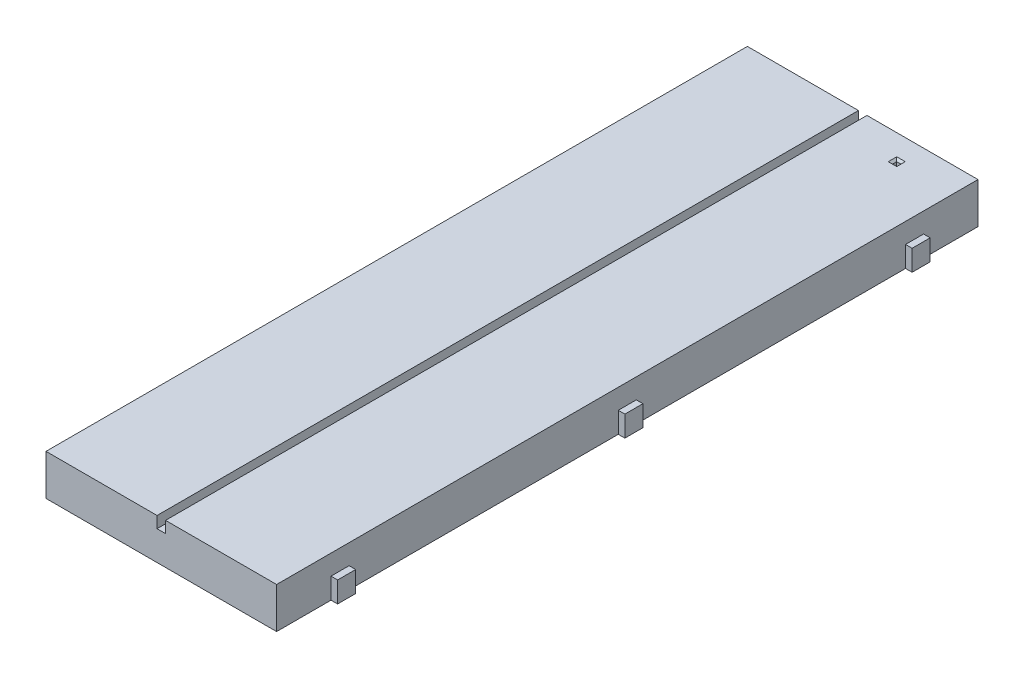
SolidWorks part; units mm, degrees
ref_plane "Front Plane" through (0, 0, 0) normal (0, 0, 1) x (1, 0, 0)
ref_plane "Top Plane" through (0, 0, 0) normal (0, 1, 0) x (1, 0, 0)
ref_plane "Right Plane" through (0, 0, 0) normal (1, 0, 0) x (0, 0, -1)
sketch "Sketch1" plane through (0, 0, 0) normal (0, 1, 0) x (1, 0, 0)
  line L1 (-27.125, -82.5) -> (27.125, -82.5)
  line L2 (-27.125, -82.5) -> (-27.125, 82.5)
  line L3 (-27.125, 82.5) -> (27.125, 82.5)
  line L4 (27.125, -82.5) -> (27.125, 82.5)
  line L5 (-27.125, -82.5) -> (27.125, 82.5) construction
  line L6 (-27.125, 82.5) -> (27.125, -82.5) construction
  point P0 (0, 0)
  dimension "D1" = 54.25
  dimension "D2" = 165
extrude "Boss-Extrude1" add sketch "Sketch1" against normal blind 9.6
sketch "Sketch2" plane through (27.125, 0, 0) normal (1, 0, 0) x (0, 0, -1)
  line L0 (82.5, -4.7) -> (69.7, -4.7)
  line L1 (82.5, -9.6) -> (82.5, 0) construction
  line L2 (-82.5, -9.6) -> (82.5, -9.6) construction
  line L3 (69.7, -4.7) -> (65.45, -4.7)
  line L4 (69.7, -4.7) -> (69.7, -9.6)
  line L5 (69.7, -9.6) -> (65.45, -9.6)
  line L6 (65.45, -4.7) -> (65.45, -9.6)
  line L7 (0, 0) -> (0, -9.6)
  line L8 (-2.125, -4.7) -> (2.125, -4.7)
  line L9 (-2.125, -4.7) -> (-2.125, -9.6)
  line L10 (-2.125, -9.6) -> (2.125, -9.6)
  line L11 (2.125, -4.7) -> (2.125, -9.6)
  line L12 (-2.125, -4.7) -> (2.125, -9.6) construction
  line L13 (-2.125, -9.6) -> (2.125, -4.7) construction
  line L14 (-69.7, -9.6) -> (-65.45, -9.6)
  line L15 (-65.45, -4.7) -> (-65.45, -9.6)
  line L16 (-69.7, -4.7) -> (-65.45, -4.7)
  line L17 (-69.7, -4.7) -> (-69.7, -9.6)
  line L18 (-69.7, -4.7) -> (-82.5, -4.8)
  line L19 (-82.5, -9.6) -> (-82.5, 0) construction
  point P9 (0, -7.15)
  line M14 (-82.5, -9.6) -> (82.5, -9.6)
  dimension "D1" = 12.8
  dimension "D2" = 4.9
  dimension "D3" = 4.25
  dimension "D4" = 4.25
  dimension "D5" = 4.9
  dimension "D6" = 12.8
extrude "Boss-Extrude2" add sketch "Sketch2" along normal blind 1.55 and the other way blind 1.55 contours L16 L17 L15 M14 | L3 L6 L4 M14 | L8 L11 L10 L9 region at (27.125, -7.15, -67.575) region at (27.125, -7.15, 67.575)
sketch "Sketch15" plane through (-27.125, 0, 0) normal (-1, 0, 0) x (0, 0, 1)
  line L0 (82.5, -9.6) -> (82.5, 0) construction
  line L2 (-82.5, -9.6) -> (82.5, -9.6) construction
  line L3 (69.7, -4.7) -> (65.45, -4.7)
  line L4 (69.7, -4.7) -> (69.7, -9.6)
  line L5 (69.7, -9.6) -> (65.45, -9.6)
  line L6 (65.45, -4.7) -> (65.45, -9.6)
  line L7 (-69.7, -9.6) -> (-65.45, -9.6)
  line L8 (-65.45, -4.7) -> (-65.45, -9.6)
  line L9 (-69.7, -4.7) -> (-65.45, -4.7)
  line L10 (-2.125, -4.7) -> (2.125, -4.7)
  line L11 (-2.125, -4.7) -> (-2.125, -9.6)
  line L12 (-2.125, -9.6) -> (2.125, -9.6)
  line L13 (2.125, -4.7) -> (2.125, -9.6)
  line L14 (-2.125, -4.7) -> (2.125, -9.6) construction
  line L15 (-2.125, -9.6) -> (2.125, -4.7) construction
  line L16 (-69.7, -4.7) -> (-69.7, -9.6)
  point P3 (0, -4.7)
  point P9 (67.575, -7.15)
  point P12 (0, -4.7)
  dimension "D1" = 4.25
  dimension "D2" = 4.9
  dimension "D3" = 12.8
  dimension "D4" = 4.25
  dimension "D5" = 4.9
extrude "Cut-Extrude1" cut sketch "Sketch15" against normal blind 1.55
sketch "Sketch17" plane through (0, 0, 0) normal (0, 1, 0) x (1, 0, 0)
  line L0 (27.125, 82.5) -> (-27.125, 82.5) construction
  line L1 (-1, -82.5) -> (1, -82.5)
  line L2 (-1, -82.5) -> (-1, 82.5)
  line L3 (-1, 82.5) -> (1, 82.5)
  line L4 (1, -82.5) -> (1, 82.5)
  line L5 (-1, -82.5) -> (1, 82.5) construction
  line L6 (-1, 82.5) -> (1, -82.5) construction
  point P0 (0, 0)
  dimension "D1" = 2
extrude "Cut-Extrude2" cut sketch "Sketch17" against normal blind 2.7
sketch "Sketch18" plane through (0, 0, 0) normal (0, 1, 0) x (1, 0, 0)
  line L0 (27.125, 82.5) -> (14.425, 82.5)
  line L1 (27.125, 82.5) -> (1, 82.5) construction
  line L2 (14.425, 82.5) -> (14.425, 77.0807)
  line L3 (11.925, 77.0807) -> (11.925, 76.0807)
  line L4 (14.425, 77.0807) -> (13.425, 77.0807)
  line L5 (14.425, 77.0807) -> (14.425, 76.0807)
  line L6 (14.425, 76.0807) -> (13.425, 76.0807)
  line L7 (13.425, 77.0807) -> (13.425, 76.0807)
  line L8 (11.925, 77.0807) -> (10.925, 77.0807)
  line L9 (10.925, 77.0807) -> (10.925, 76.0807)
  line L10 (11.925, 76.0807) -> (10.925, 76.0807)
  line L11 (9.425, 77.0807) -> (9.425, 76.0807)
  line L12 (9.425, 77.0807) -> (8.425, 77.0807)
  line L13 (8.425, 77.0807) -> (8.425, 76.0807)
  line L14 (9.425, 76.0807) -> (8.425, 76.0807)
  line L15 (6.925, 77.0807) -> (6.925, 76.0807)
  line L16 (6.925, 77.0807) -> (5.925, 77.0807)
  line L17 (5.925, 77.0807) -> (5.925, 76.0807)
  line L18 (6.925, 76.0807) -> (5.925, 76.0807)
  line L19 (4.425, 77.0807) -> (4.425, 76.0807)
  line L20 (4.425, 77.0807) -> (3.425, 77.0807)
  line L21 (3.425, 77.0807) -> (3.425, 76.0807)
  line L22 (4.425, 76.0807) -> (3.425, 76.0807)
  line L23 (11.925, 74.5807) -> (11.925, 73.5807)
  line L24 (11.925, 74.5807) -> (10.925, 74.5807)
  line L25 (10.925, 74.5807) -> (10.925, 73.5807)
  line L26 (11.925, 73.5807) -> (10.925, 73.5807)
  line L27 (9.425, 74.5807) -> (9.425, 73.5807)
  line L28 (9.425, 74.5807) -> (8.425, 74.5807)
  line L29 (8.425, 74.5807) -> (8.425, 73.5807)
  line L30 (9.425, 73.5807) -> (8.425, 73.5807)
  line L31 (6.925, 74.5807) -> (6.925, 73.5807)
  line L32 (6.925, 74.5807) -> (5.925, 74.5807)
  line L33 (5.925, 74.5807) -> (5.925, 73.5807)
  line L34 (6.925, 73.5807) -> (5.925, 73.5807)
  line L35 (4.425, 74.5807) -> (4.425, 73.5807)
  line L36 (4.425, 74.5807) -> (3.425, 74.5807)
  line L37 (3.425, 74.5807) -> (3.425, 73.5807)
  line L38 (4.425, 73.5807) -> (3.425, 73.5807)
  line L39 (11.925, 72.0807) -> (11.925, 71.0807)
  line L40 (11.925, 72.0807) -> (10.925, 72.0807)
  line L41 (10.925, 72.0807) -> (10.925, 71.0807)
  line L42 (11.925, 71.0807) -> (10.925, 71.0807)
  line L43 (9.425, 72.0807) -> (9.425, 71.0807)
  line L44 (9.425, 72.0807) -> (8.425, 72.0807)
  line L45 (8.425, 72.0807) -> (8.425, 71.0807)
  line L46 (9.425, 71.0807) -> (8.425, 71.0807)
  line L47 (6.925, 72.0807) -> (6.925, 71.0807)
  line L48 (6.925, 72.0807) -> (5.925, 72.0807)
  line L49 (5.925, 72.0807) -> (5.925, 71.0807)
  line L50 (6.925, 71.0807) -> (5.925, 71.0807)
  line L51 (4.425, 72.0807) -> (4.425, 71.0807)
  line L52 (4.425, 72.0807) -> (3.425, 72.0807)
  line L53 (3.425, 72.0807) -> (3.425, 71.0807)
  line L54 (4.425, 71.0807) -> (3.425, 71.0807)
  line L55 (11.925, 69.5807) -> (11.925, 68.5807)
  line L56 (11.925, 69.5807) -> (10.925, 69.5807)
  line L57 (10.925, 69.5807) -> (10.925, 68.5807)
  line L58 (11.925, 68.5807) -> (10.925, 68.5807)
  line L59 (9.425, 69.5807) -> (9.425, 68.5807)
  line L60 (9.425, 69.5807) -> (8.425, 69.5807)
  line L61 (8.425, 69.5807) -> (8.425, 68.5807)
  line L62 (9.425, 68.5807) -> (8.425, 68.5807)
  line L63 (6.925, 69.5807) -> (6.925, 68.5807)
  line L64 (6.925, 69.5807) -> (5.925, 69.5807)
  line L65 (5.925, 69.5807) -> (5.925, 68.5807)
  line L66 (6.925, 68.5807) -> (5.925, 68.5807)
  line L67 (4.425, 69.5807) -> (4.425, 68.5807)
  line L68 (4.425, 69.5807) -> (3.425, 69.5807)
  line L69 (3.425, 69.5807) -> (3.425, 68.5807)
  line L70 (4.425, 68.5807) -> (3.425, 68.5807)
  line L71 (11.925, 67.0807) -> (11.925, 66.0807)
  line L72 (11.925, 67.0807) -> (10.925, 67.0807)
  line L73 (10.925, 67.0807) -> (10.925, 66.0807)
  line L74 (11.925, 66.0807) -> (10.925, 66.0807)
  line L75 (9.425, 67.0807) -> (9.425, 66.0807)
  line L76 (9.425, 67.0807) -> (8.425, 67.0807)
  line L77 (8.425, 67.0807) -> (8.425, 66.0807)
  line L78 (9.425, 66.0807) -> (8.425, 66.0807)
  line L79 (6.925, 67.0807) -> (6.925, 66.0807)
  line L80 (6.925, 67.0807) -> (5.925, 67.0807)
  line L81 (5.925, 67.0807) -> (5.925, 66.0807)
  line L82 (6.925, 66.0807) -> (5.925, 66.0807)
  line L83 (4.425, 67.0807) -> (4.425, 66.0807)
  line L84 (4.425, 67.0807) -> (3.425, 67.0807)
  line L85 (3.425, 67.0807) -> (3.425, 66.0807)
  line L86 (4.425, 66.0807) -> (3.425, 66.0807)
  line L87 (11.925, 64.5807) -> (11.925, 63.5807)
  line L88 (11.925, 64.5807) -> (10.925, 64.5807)
  line L89 (10.925, 64.5807) -> (10.925, 63.5807)
  line L90 (11.925, 63.5807) -> (10.925, 63.5807)
  line L91 (9.425, 64.5807) -> (9.425, 63.5807)
  line L92 (9.425, 64.5807) -> (8.425, 64.5807)
  line L93 (8.425, 64.5807) -> (8.425, 63.5807)
  line L94 (9.425, 63.5807) -> (8.425, 63.5807)
  line L95 (6.925, 64.5807) -> (6.925, 63.5807)
  line L96 (6.925, 64.5807) -> (5.925, 64.5807)
  line L97 (5.925, 64.5807) -> (5.925, 63.5807)
  line L98 (6.925, 63.5807) -> (5.925, 63.5807)
  line L99 (4.425, 64.5807) -> (4.425, 63.5807)
  line L100 (4.425, 64.5807) -> (3.425, 64.5807)
  line L101 (3.425, 64.5807) -> (3.425, 63.5807)
  line L102 (4.425, 63.5807) -> (3.425, 63.5807)
  line L103 (11.925, 62.0807) -> (11.925, 61.0807)
  line L104 (11.925, 62.0807) -> (10.925, 62.0807)
  line L105 (10.925, 62.0807) -> (10.925, 61.0807)
  line L106 (11.925, 61.0807) -> (10.925, 61.0807)
  line L107 (9.425, 62.0807) -> (9.425, 61.0807)
  line L108 (9.425, 62.0807) -> (8.425, 62.0807)
  line L109 (8.425, 62.0807) -> (8.425, 61.0807)
  line L110 (9.425, 61.0807) -> (8.425, 61.0807)
  line L111 (6.925, 62.0807) -> (6.925, 61.0807)
  line L112 (6.925, 62.0807) -> (5.925, 62.0807)
  line L113 (5.925, 62.0807) -> (5.925, 61.0807)
  line L114 (6.925, 61.0807) -> (5.925, 61.0807)
  line L115 (4.425, 62.0807) -> (4.425, 61.0807)
  line L116 (4.425, 62.0807) -> (3.425, 62.0807)
  line L117 (3.425, 62.0807) -> (3.425, 61.0807)
  line L118 (4.425, 61.0807) -> (3.425, 61.0807)
  line L119 (11.925, 59.5807) -> (11.925, 58.5807)
  line L120 (11.925, 59.5807) -> (10.925, 59.5807)
  line L121 (10.925, 59.5807) -> (10.925, 58.5807)
  line L122 (11.925, 58.5807) -> (10.925, 58.5807)
  line L123 (9.425, 59.5807) -> (9.425, 58.5807)
  line L124 (9.425, 59.5807) -> (8.425, 59.5807)
  line L125 (8.425, 59.5807) -> (8.425, 58.5807)
  line L126 (9.425, 58.5807) -> (8.425, 58.5807)
  line L127 (6.925, 59.5807) -> (6.925, 58.5807)
  line L128 (6.925, 59.5807) -> (5.925, 59.5807)
  line L129 (5.925, 59.5807) -> (5.925, 58.5807)
  line L130 (6.925, 58.5807) -> (5.925, 58.5807)
  line L131 (4.425, 59.5807) -> (4.425, 58.5807)
  line L132 (4.425, 59.5807) -> (3.425, 59.5807)
  line L133 (3.425, 59.5807) -> (3.425, 58.5807)
  line L134 (4.425, 58.5807) -> (3.425, 58.5807)
  line L135 (11.925, 57.0807) -> (11.925, 56.0807)
  line L136 (11.925, 57.0807) -> (10.925, 57.0807)
  line L137 (10.925, 57.0807) -> (10.925, 56.0807)
  line L138 (11.925, 56.0807) -> (10.925, 56.0807)
  line L139 (9.425, 57.0807) -> (9.425, 56.0807)
  line L140 (9.425, 57.0807) -> (8.425, 57.0807)
  line L141 (8.425, 57.0807) -> (8.425, 56.0807)
  line L142 (9.425, 56.0807) -> (8.425, 56.0807)
  line L143 (6.925, 57.0807) -> (6.925, 56.0807)
  line L144 (6.925, 57.0807) -> (5.925, 57.0807)
  line L145 (5.925, 57.0807) -> (5.925, 56.0807)
  line L146 (6.925, 56.0807) -> (5.925, 56.0807)
  line L147 (4.425, 57.0807) -> (4.425, 56.0807)
  line L148 (4.425, 57.0807) -> (3.425, 57.0807)
  line L149 (3.425, 57.0807) -> (3.425, 56.0807)
  line L150 (4.425, 56.0807) -> (3.425, 56.0807)
  line L151 (11.925, 54.5807) -> (11.925, 53.5807)
  line L152 (11.925, 54.5807) -> (10.925, 54.5807)
  line L153 (10.925, 54.5807) -> (10.925, 53.5807)
  line L154 (11.925, 53.5807) -> (10.925, 53.5807)
  line L155 (9.425, 54.5807) -> (9.425, 53.5807)
  line L156 (9.425, 54.5807) -> (8.425, 54.5807)
  line L157 (8.425, 54.5807) -> (8.425, 53.5807)
  line L158 (9.425, 53.5807) -> (8.425, 53.5807)
  line L159 (6.925, 54.5807) -> (6.925, 53.5807)
  line L160 (6.925, 54.5807) -> (5.925, 54.5807)
  line L161 (5.925, 54.5807) -> (5.925, 53.5807)
  line L162 (6.925, 53.5807) -> (5.925, 53.5807)
  line L163 (4.425, 54.5807) -> (4.425, 53.5807)
  line L164 (4.425, 54.5807) -> (3.425, 54.5807)
  line L165 (3.425, 54.5807) -> (3.425, 53.5807)
  line L166 (4.425, 53.5807) -> (3.425, 53.5807)
  line L167 (11.925, 52.0807) -> (11.925, 51.0807)
  line L168 (11.925, 52.0807) -> (10.925, 52.0807)
  line L169 (10.925, 52.0807) -> (10.925, 51.0807)
  line L170 (11.925, 51.0807) -> (10.925, 51.0807)
  line L171 (9.425, 52.0807) -> (9.425, 51.0807)
  line L172 (9.425, 52.0807) -> (8.425, 52.0807)
  line L173 (8.425, 52.0807) -> (8.425, 51.0807)
  line L174 (9.425, 51.0807) -> (8.425, 51.0807)
  line L175 (6.925, 52.0807) -> (6.925, 51.0807)
  line L176 (6.925, 52.0807) -> (5.925, 52.0807)
  line L177 (5.925, 52.0807) -> (5.925, 51.0807)
  line L178 (6.925, 51.0807) -> (5.925, 51.0807)
  line L179 (4.425, 52.0807) -> (4.425, 51.0807)
  line L180 (4.425, 52.0807) -> (3.425, 52.0807)
  line L181 (3.425, 52.0807) -> (3.425, 51.0807)
  line L182 (4.425, 51.0807) -> (3.425, 51.0807)
  line L183 (11.925, 49.5807) -> (11.925, 48.5807)
  line L184 (11.925, 49.5807) -> (10.925, 49.5807)
  line L185 (10.925, 49.5807) -> (10.925, 48.5807)
  line L186 (11.925, 48.5807) -> (10.925, 48.5807)
  line L187 (9.425, 49.5807) -> (9.425, 48.5807)
  line L188 (9.425, 49.5807) -> (8.425, 49.5807)
  line L189 (8.425, 49.5807) -> (8.425, 48.5807)
  line L190 (9.425, 48.5807) -> (8.425, 48.5807)
  line L191 (6.925, 49.5807) -> (6.925, 48.5807)
  line L192 (6.925, 49.5807) -> (5.925, 49.5807)
  line L193 (5.925, 49.5807) -> (5.925, 48.5807)
  line L194 (6.925, 48.5807) -> (5.925, 48.5807)
  line L195 (4.425, 49.5807) -> (4.425, 48.5807)
  line L196 (4.425, 49.5807) -> (3.425, 49.5807)
  line L197 (3.425, 49.5807) -> (3.425, 48.5807)
  line L198 (4.425, 48.5807) -> (3.425, 48.5807)
  line L199 (11.925, 47.0807) -> (11.925, 46.0807)
  line L200 (11.925, 47.0807) -> (10.925, 47.0807)
  line L201 (10.925, 47.0807) -> (10.925, 46.0807)
  line L202 (11.925, 46.0807) -> (10.925, 46.0807)
  line L203 (9.425, 47.0807) -> (9.425, 46.0807)
  line L204 (9.425, 47.0807) -> (8.425, 47.0807)
  line L205 (8.425, 47.0807) -> (8.425, 46.0807)
  line L206 (9.425, 46.0807) -> (8.425, 46.0807)
  line L207 (6.925, 47.0807) -> (6.925, 46.0807)
  line L208 (6.925, 47.0807) -> (5.925, 47.0807)
  line L209 (5.925, 47.0807) -> (5.925, 46.0807)
  line L210 (6.925, 46.0807) -> (5.925, 46.0807)
  line L211 (4.425, 47.0807) -> (4.425, 46.0807)
  line L212 (4.425, 47.0807) -> (3.425, 47.0807)
  line L213 (3.425, 47.0807) -> (3.425, 46.0807)
  line L214 (4.425, 46.0807) -> (3.425, 46.0807)
  line L215 (11.925, 44.5807) -> (11.925, 43.5807)
  line L216 (11.925, 44.5807) -> (10.925, 44.5807)
  line L217 (10.925, 44.5807) -> (10.925, 43.5807)
  line L218 (11.925, 43.5807) -> (10.925, 43.5807)
  line L219 (9.425, 44.5807) -> (9.425, 43.5807)
  line L220 (9.425, 44.5807) -> (8.425, 44.5807)
  line L221 (8.425, 44.5807) -> (8.425, 43.5807)
  line L222 (9.425, 43.5807) -> (8.425, 43.5807)
  line L223 (6.925, 44.5807) -> (6.925, 43.5807)
  line L224 (6.925, 44.5807) -> (5.925, 44.5807)
  line L225 (5.925, 44.5807) -> (5.925, 43.5807)
  line L226 (6.925, 43.5807) -> (5.925, 43.5807)
  line L227 (4.425, 44.5807) -> (4.425, 43.5807)
  line L228 (4.425, 44.5807) -> (3.425, 44.5807)
  line L229 (3.425, 44.5807) -> (3.425, 43.5807)
  line L230 (4.425, 43.5807) -> (3.425, 43.5807)
  line L231 (11.925, 42.0807) -> (11.925, 41.0807)
  line L232 (11.925, 42.0807) -> (10.925, 42.0807)
  line L233 (10.925, 42.0807) -> (10.925, 41.0807)
  line L234 (11.925, 41.0807) -> (10.925, 41.0807)
  line L235 (9.425, 42.0807) -> (9.425, 41.0807)
  line L236 (9.425, 42.0807) -> (8.425, 42.0807)
  line L237 (8.425, 42.0807) -> (8.425, 41.0807)
  line L238 (9.425, 41.0807) -> (8.425, 41.0807)
  line L239 (6.925, 42.0807) -> (6.925, 41.0807)
  line L240 (6.925, 42.0807) -> (5.925, 42.0807)
  line L241 (5.925, 42.0807) -> (5.925, 41.0807)
  line L242 (6.925, 41.0807) -> (5.925, 41.0807)
  line L243 (4.425, 42.0807) -> (4.425, 41.0807)
  line L244 (4.425, 42.0807) -> (3.425, 42.0807)
  line L245 (3.425, 42.0807) -> (3.425, 41.0807)
  line L246 (4.425, 41.0807) -> (3.425, 41.0807)
  line L247 (11.925, 39.5807) -> (11.925, 38.5807)
  line L248 (11.925, 39.5807) -> (10.925, 39.5807)
  line L249 (10.925, 39.5807) -> (10.925, 38.5807)
  line L250 (11.925, 38.5807) -> (10.925, 38.5807)
  line L251 (9.425, 39.5807) -> (9.425, 38.5807)
  line L252 (9.425, 39.5807) -> (8.425, 39.5807)
  line L253 (8.425, 39.5807) -> (8.425, 38.5807)
  line L254 (9.425, 38.5807) -> (8.425, 38.5807)
  line L255 (6.925, 39.5807) -> (6.925, 38.5807)
  line L256 (6.925, 39.5807) -> (5.925, 39.5807)
  line L257 (5.925, 39.5807) -> (5.925, 38.5807)
  line L258 (6.925, 38.5807) -> (5.925, 38.5807)
  line L259 (4.425, 39.5807) -> (4.425, 38.5807)
  line L260 (4.425, 39.5807) -> (3.425, 39.5807)
  line L261 (3.425, 39.5807) -> (3.425, 38.5807)
  line L262 (4.425, 38.5807) -> (3.425, 38.5807)
  line L263 (11.925, 37.0807) -> (11.925, 36.0807)
  line L264 (11.925, 37.0807) -> (10.925, 37.0807)
  line L265 (10.925, 37.0807) -> (10.925, 36.0807)
  line L266 (11.925, 36.0807) -> (10.925, 36.0807)
  line L267 (9.425, 37.0807) -> (9.425, 36.0807)
  line L268 (9.425, 37.0807) -> (8.425, 37.0807)
  line L269 (8.425, 37.0807) -> (8.425, 36.0807)
  line L270 (9.425, 36.0807) -> (8.425, 36.0807)
  line L271 (6.925, 37.0807) -> (6.925, 36.0807)
  line L272 (6.925, 37.0807) -> (5.925, 37.0807)
  line L273 (5.925, 37.0807) -> (5.925, 36.0807)
  line L274 (6.925, 36.0807) -> (5.925, 36.0807)
  line L275 (4.425, 37.0807) -> (4.425, 36.0807)
  line L276 (4.425, 37.0807) -> (3.425, 37.0807)
  line L277 (3.425, 37.0807) -> (3.425, 36.0807)
  line L278 (4.425, 36.0807) -> (3.425, 36.0807)
  line L279 (11.925, 34.5807) -> (11.925, 33.5807)
  line L280 (11.925, 34.5807) -> (10.925, 34.5807)
  line L281 (10.925, 34.5807) -> (10.925, 33.5807)
  line L282 (11.925, 33.5807) -> (10.925, 33.5807)
  line L283 (9.425, 34.5807) -> (9.425, 33.5807)
  line L284 (9.425, 34.5807) -> (8.425, 34.5807)
  line L285 (8.425, 34.5807) -> (8.425, 33.5807)
  line L286 (9.425, 33.5807) -> (8.425, 33.5807)
  line L287 (6.925, 34.5807) -> (6.925, 33.5807)
  line L288 (6.925, 34.5807) -> (5.925, 34.5807)
  line L289 (5.925, 34.5807) -> (5.925, 33.5807)
  line L290 (6.925, 33.5807) -> (5.925, 33.5807)
  line L291 (4.425, 34.5807) -> (4.425, 33.5807)
  line L292 (4.425, 34.5807) -> (3.425, 34.5807)
  line L293 (3.425, 34.5807) -> (3.425, 33.5807)
  line L294 (4.425, 33.5807) -> (3.425, 33.5807)
  line L295 (11.925, 32.0807) -> (11.925, 31.0807)
  line L296 (11.925, 32.0807) -> (10.925, 32.0807)
  line L297 (10.925, 32.0807) -> (10.925, 31.0807)
  line L298 (11.925, 31.0807) -> (10.925, 31.0807)
  line L299 (9.425, 32.0807) -> (9.425, 31.0807)
  line L300 (9.425, 32.0807) -> (8.425, 32.0807)
  line L301 (8.425, 32.0807) -> (8.425, 31.0807)
  line L302 (9.425, 31.0807) -> (8.425, 31.0807)
  line L303 (6.925, 32.0807) -> (6.925, 31.0807)
  line L304 (6.925, 32.0807) -> (5.925, 32.0807)
  line L305 (5.925, 32.0807) -> (5.925, 31.0807)
  line L306 (6.925, 31.0807) -> (5.925, 31.0807)
  line L307 (4.425, 32.0807) -> (4.425, 31.0807)
  line L308 (4.425, 32.0807) -> (3.425, 32.0807)
  line L309 (3.425, 32.0807) -> (3.425, 31.0807)
  line L310 (4.425, 31.0807) -> (3.425, 31.0807)
  line L311 (11.925, 29.5807) -> (11.925, 28.5807)
  line L312 (11.925, 29.5807) -> (10.925, 29.5807)
  line L313 (10.925, 29.5807) -> (10.925, 28.5807)
  line L314 (11.925, 28.5807) -> (10.925, 28.5807)
  line L315 (9.425, 29.5807) -> (9.425, 28.5807)
  line L316 (9.425, 29.5807) -> (8.425, 29.5807)
  line L317 (8.425, 29.5807) -> (8.425, 28.5807)
  line L318 (9.425, 28.5807) -> (8.425, 28.5807)
  line L319 (6.925, 29.5807) -> (6.925, 28.5807)
  line L320 (6.925, 29.5807) -> (5.925, 29.5807)
  line L321 (5.925, 29.5807) -> (5.925, 28.5807)
  line L322 (6.925, 28.5807) -> (5.925, 28.5807)
  line L323 (4.425, 29.5807) -> (4.425, 28.5807)
  line L324 (4.425, 29.5807) -> (3.425, 29.5807)
  line L325 (3.425, 29.5807) -> (3.425, 28.5807)
  line L326 (4.425, 28.5807) -> (3.425, 28.5807)
  line L327 (11.925, 27.0807) -> (11.925, 26.0807)
  line L328 (11.925, 27.0807) -> (10.925, 27.0807)
  line L329 (10.925, 27.0807) -> (10.925, 26.0807)
  line L330 (11.925, 26.0807) -> (10.925, 26.0807)
  line L331 (9.425, 27.0807) -> (9.425, 26.0807)
  line L332 (9.425, 27.0807) -> (8.425, 27.0807)
  line L333 (8.425, 27.0807) -> (8.425, 26.0807)
  line L334 (9.425, 26.0807) -> (8.425, 26.0807)
  line L335 (6.925, 27.0807) -> (6.925, 26.0807)
  line L336 (6.925, 27.0807) -> (5.925, 27.0807)
  line L337 (5.925, 27.0807) -> (5.925, 26.0807)
  line L338 (6.925, 26.0807) -> (5.925, 26.0807)
  line L339 (4.425, 27.0807) -> (4.425, 26.0807)
  line L340 (4.425, 27.0807) -> (3.425, 27.0807)
  line L341 (3.425, 27.0807) -> (3.425, 26.0807)
  line L342 (4.425, 26.0807) -> (3.425, 26.0807)
  line L343 (11.925, 24.5807) -> (11.925, 23.5807)
  line L344 (11.925, 24.5807) -> (10.925, 24.5807)
  line L345 (10.925, 24.5807) -> (10.925, 23.5807)
  line L346 (11.925, 23.5807) -> (10.925, 23.5807)
  line L347 (9.425, 24.5807) -> (9.425, 23.5807)
  line L348 (9.425, 24.5807) -> (8.425, 24.5807)
  line L349 (8.425, 24.5807) -> (8.425, 23.5807)
  line L350 (9.425, 23.5807) -> (8.425, 23.5807)
  line L351 (6.925, 24.5807) -> (6.925, 23.5807)
  line L352 (6.925, 24.5807) -> (5.925, 24.5807)
  line L353 (5.925, 24.5807) -> (5.925, 23.5807)
  line L354 (6.925, 23.5807) -> (5.925, 23.5807)
  line L355 (4.425, 24.5807) -> (4.425, 23.5807)
  line L356 (4.425, 24.5807) -> (3.425, 24.5807)
  line L357 (3.425, 24.5807) -> (3.425, 23.5807)
  line L358 (4.425, 23.5807) -> (3.425, 23.5807)
  line L359 (11.925, 22.0807) -> (11.925, 21.0807)
  line L360 (11.925, 22.0807) -> (10.925, 22.0807)
  line L361 (10.925, 22.0807) -> (10.925, 21.0807)
  line L362 (11.925, 21.0807) -> (10.925, 21.0807)
  line L363 (9.425, 22.0807) -> (9.425, 21.0807)
  line L364 (9.425, 22.0807) -> (8.425, 22.0807)
  line L365 (8.425, 22.0807) -> (8.425, 21.0807)
  line L366 (9.425, 21.0807) -> (8.425, 21.0807)
  line L367 (6.925, 22.0807) -> (6.925, 21.0807)
  line L368 (6.925, 22.0807) -> (5.925, 22.0807)
  line L369 (5.925, 22.0807) -> (5.925, 21.0807)
  line L370 (6.925, 21.0807) -> (5.925, 21.0807)
  line L371 (4.425, 22.0807) -> (4.425, 21.0807)
  line L372 (4.425, 22.0807) -> (3.425, 22.0807)
  line L373 (3.425, 22.0807) -> (3.425, 21.0807)
  line L374 (4.425, 21.0807) -> (3.425, 21.0807)
  line L375 (11.925, 19.5807) -> (11.925, 18.5807)
  line L376 (11.925, 19.5807) -> (10.925, 19.5807)
  line L377 (10.925, 19.5807) -> (10.925, 18.5807)
  line L378 (11.925, 18.5807) -> (10.925, 18.5807)
  line L379 (9.425, 19.5807) -> (9.425, 18.5807)
  line L380 (9.425, 19.5807) -> (8.425, 19.5807)
  line L381 (8.425, 19.5807) -> (8.425, 18.5807)
  line L382 (9.425, 18.5807) -> (8.425, 18.5807)
  line L383 (6.925, 19.5807) -> (6.925, 18.5807)
  line L384 (6.925, 19.5807) -> (5.925, 19.5807)
  line L385 (5.925, 19.5807) -> (5.925, 18.5807)
  line L386 (6.925, 18.5807) -> (5.925, 18.5807)
  line L387 (4.425, 19.5807) -> (4.425, 18.5807)
  line L388 (4.425, 19.5807) -> (3.425, 19.5807)
  line L389 (3.425, 19.5807) -> (3.425, 18.5807)
  line L390 (4.425, 18.5807) -> (3.425, 18.5807)
  line L391 (11.925, 17.0807) -> (11.925, 16.0807)
  line L392 (11.925, 17.0807) -> (10.925, 17.0807)
  line L393 (10.925, 17.0807) -> (10.925, 16.0807)
  line L394 (11.925, 16.0807) -> (10.925, 16.0807)
  line L395 (9.425, 17.0807) -> (9.425, 16.0807)
  line L396 (9.425, 17.0807) -> (8.425, 17.0807)
  line L397 (8.425, 17.0807) -> (8.425, 16.0807)
  line L398 (9.425, 16.0807) -> (8.425, 16.0807)
  line L399 (6.925, 17.0807) -> (6.925, 16.0807)
  line L400 (6.925, 17.0807) -> (5.925, 17.0807)
  line L401 (5.925, 17.0807) -> (5.925, 16.0807)
  line L402 (6.925, 16.0807) -> (5.925, 16.0807)
  line L403 (4.425, 17.0807) -> (4.425, 16.0807)
  line L404 (4.425, 17.0807) -> (3.425, 17.0807)
  line L405 (3.425, 17.0807) -> (3.425, 16.0807)
  line L406 (4.425, 16.0807) -> (3.425, 16.0807)
  line L407 (11.925, 14.5807) -> (11.925, 13.5807)
  line L408 (11.925, 14.5807) -> (10.925, 14.5807)
  line L409 (10.925, 14.5807) -> (10.925, 13.5807)
  line L410 (11.925, 13.5807) -> (10.925, 13.5807)
  line L411 (9.425, 14.5807) -> (9.425, 13.5807)
  line L412 (9.425, 14.5807) -> (8.425, 14.5807)
  line L413 (8.425, 14.5807) -> (8.425, 13.5807)
  line L414 (9.425, 13.5807) -> (8.425, 13.5807)
  line L415 (6.925, 14.5807) -> (6.925, 13.5807)
  line L416 (6.925, 14.5807) -> (5.925, 14.5807)
  line L417 (5.925, 14.5807) -> (5.925, 13.5807)
  line L418 (6.925, 13.5807) -> (5.925, 13.5807)
  line L419 (4.425, 14.5807) -> (4.425, 13.5807)
  line L420 (4.425, 14.5807) -> (3.425, 14.5807)
  line L421 (3.425, 14.5807) -> (3.425, 13.5807)
  line L422 (4.425, 13.5807) -> (3.425, 13.5807)
  line L423 (11.925, 12.0807) -> (11.925, 11.0807)
  line L424 (11.925, 12.0807) -> (10.925, 12.0807)
  line L425 (10.925, 12.0807) -> (10.925, 11.0807)
  line L426 (11.925, 11.0807) -> (10.925, 11.0807)
  line L427 (9.425, 12.0807) -> (9.425, 11.0807)
  line L428 (9.425, 12.0807) -> (8.425, 12.0807)
  line L429 (8.425, 12.0807) -> (8.425, 11.0807)
  line L430 (9.425, 11.0807) -> (8.425, 11.0807)
  line L431 (6.925, 12.0807) -> (6.925, 11.0807)
  line L432 (6.925, 12.0807) -> (5.925, 12.0807)
  line L433 (5.925, 12.0807) -> (5.925, 11.0807)
  line L434 (6.925, 11.0807) -> (5.925, 11.0807)
  line L435 (4.425, 12.0807) -> (4.425, 11.0807)
  line L436 (4.425, 12.0807) -> (3.425, 12.0807)
  line L437 (3.425, 12.0807) -> (3.425, 11.0807)
  line L438 (4.425, 11.0807) -> (3.425, 11.0807)
  line L439 (11.925, 9.5807) -> (11.925, 8.5807)
  line L440 (11.925, 9.5807) -> (10.925, 9.5807)
  line L441 (10.925, 9.5807) -> (10.925, 8.5807)
  line L442 (11.925, 8.5807) -> (10.925, 8.5807)
  line L443 (9.425, 9.5807) -> (9.425, 8.5807)
  line L444 (9.425, 9.5807) -> (8.425, 9.5807)
  line L445 (8.425, 9.5807) -> (8.425, 8.5807)
  line L446 (9.425, 8.5807) -> (8.425, 8.5807)
  line L447 (6.925, 9.5807) -> (6.925, 8.5807)
  line L448 (6.925, 9.5807) -> (5.925, 9.5807)
  line L449 (5.925, 9.5807) -> (5.925, 8.5807)
  line L450 (6.925, 8.5807) -> (5.925, 8.5807)
  line L451 (4.425, 9.5807) -> (4.425, 8.5807)
  line L452 (4.425, 9.5807) -> (3.425, 9.5807)
  line L453 (3.425, 9.5807) -> (3.425, 8.5807)
  line L454 (4.425, 8.5807) -> (3.425, 8.5807)
  line L455 (11.925, 7.0807) -> (11.925, 6.0807)
  line L456 (11.925, 7.0807) -> (10.925, 7.0807)
  line L457 (10.925, 7.0807) -> (10.925, 6.0807)
  line L458 (11.925, 6.0807) -> (10.925, 6.0807)
  line L459 (9.425, 7.0807) -> (9.425, 6.0807)
  line L460 (9.425, 7.0807) -> (8.425, 7.0807)
  line L461 (8.425, 7.0807) -> (8.425, 6.0807)
  line L462 (9.425, 6.0807) -> (8.425, 6.0807)
  line L463 (6.925, 7.0807) -> (6.925, 6.0807)
  line L464 (6.925, 7.0807) -> (5.925, 7.0807)
  line L465 (5.925, 7.0807) -> (5.925, 6.0807)
  line L466 (6.925, 6.0807) -> (5.925, 6.0807)
  line L467 (4.425, 7.0807) -> (4.425, 6.0807)
  line L468 (4.425, 7.0807) -> (3.425, 7.0807)
  line L469 (3.425, 7.0807) -> (3.425, 6.0807)
  line L470 (4.425, 6.0807) -> (3.425, 6.0807)
  line L471 (11.925, 4.5807) -> (11.925, 3.5807)
  line L472 (11.925, 4.5807) -> (10.925, 4.5807)
  line L473 (10.925, 4.5807) -> (10.925, 3.5807)
  line L474 (11.925, 3.5807) -> (10.925, 3.5807)
  line L475 (9.425, 4.5807) -> (9.425, 3.5807)
  line L476 (9.425, 4.5807) -> (8.425, 4.5807)
  line L477 (8.425, 4.5807) -> (8.425, 3.5807)
  line L478 (9.425, 3.5807) -> (8.425, 3.5807)
  line L479 (6.925, 4.5807) -> (6.925, 3.5807)
  line L480 (6.925, 4.5807) -> (5.925, 4.5807)
  line L481 (5.925, 4.5807) -> (5.925, 3.5807)
  line L482 (6.925, 3.5807) -> (5.925, 3.5807)
  line L483 (4.425, 4.5807) -> (4.425, 3.5807)
  line L484 (4.425, 4.5807) -> (3.425, 4.5807)
  line L485 (3.425, 4.5807) -> (3.425, 3.5807)
  line L486 (4.425, 3.5807) -> (3.425, 3.5807)
  line L487 (11.925, 2.0807) -> (11.925, 1.0807)
  line L488 (11.925, 2.0807) -> (10.925, 2.0807)
  line L489 (10.925, 2.0807) -> (10.925, 1.0807)
  line L490 (11.925, 1.0807) -> (10.925, 1.0807)
  line L491 (9.425, 2.0807) -> (9.425, 1.0807)
  line L492 (9.425, 2.0807) -> (8.425, 2.0807)
  line L493 (8.425, 2.0807) -> (8.425, 1.0807)
  line L494 (9.425, 1.0807) -> (8.425, 1.0807)
  line L495 (6.925, 2.0807) -> (6.925, 1.0807)
  line L496 (6.925, 2.0807) -> (5.925, 2.0807)
  line L497 (5.925, 2.0807) -> (5.925, 1.0807)
  line L498 (6.925, 1.0807) -> (5.925, 1.0807)
  line L499 (4.425, 2.0807) -> (4.425, 1.0807)
  line L500 (4.425, 2.0807) -> (3.425, 2.0807)
  line L501 (3.425, 2.0807) -> (3.425, 1.0807)
  line L502 (4.425, 1.0807) -> (3.425, 1.0807)
  line L503 (11.925, -0.4193) -> (11.925, -1.4193)
  line L504 (11.925, -0.4193) -> (10.925, -0.4193)
  line L505 (10.925, -0.4193) -> (10.925, -1.4193)
  line L506 (11.925, -1.4193) -> (10.925, -1.4193)
  line L507 (9.425, -0.4193) -> (9.425, -1.4193)
  line L508 (9.425, -0.4193) -> (8.425, -0.4193)
  line L509 (8.425, -0.4193) -> (8.425, -1.4193)
  line L510 (9.425, -1.4193) -> (8.425, -1.4193)
  line L511 (6.925, -0.4193) -> (6.925, -1.4193)
  line L512 (6.925, -0.4193) -> (5.925, -0.4193)
  line L513 (5.925, -0.4193) -> (5.925, -1.4193)
  line L514 (6.925, -1.4193) -> (5.925, -1.4193)
  line L515 (4.425, -0.4193) -> (4.425, -1.4193)
  line L516 (4.425, -0.4193) -> (3.425, -0.4193)
  line L517 (3.425, -0.4193) -> (3.425, -1.4193)
  line L518 (4.425, -1.4193) -> (3.425, -1.4193)
  line L519 (11.925, -2.9193) -> (11.925, -3.9193)
  line L520 (11.925, -2.9193) -> (10.925, -2.9193)
  line L521 (10.925, -2.9193) -> (10.925, -3.9193)
  line L522 (11.925, -3.9193) -> (10.925, -3.9193)
  line L523 (9.425, -2.9193) -> (9.425, -3.9193)
  line L524 (9.425, -2.9193) -> (8.425, -2.9193)
  line L525 (8.425, -2.9193) -> (8.425, -3.9193)
  line L526 (9.425, -3.9193) -> (8.425, -3.9193)
  line L527 (6.925, -2.9193) -> (6.925, -3.9193)
  line L528 (6.925, -2.9193) -> (5.925, -2.9193)
  line L529 (5.925, -2.9193) -> (5.925, -3.9193)
  line L530 (6.925, -3.9193) -> (5.925, -3.9193)
  line L531 (4.425, -2.9193) -> (4.425, -3.9193)
  line L532 (4.425, -2.9193) -> (3.425, -2.9193)
  line L533 (3.425, -2.9193) -> (3.425, -3.9193)
  line L534 (4.425, -3.9193) -> (3.425, -3.9193)
  line L535 (11.925, -5.4193) -> (11.925, -6.4193)
  line L536 (11.925, -5.4193) -> (10.925, -5.4193)
  line L537 (10.925, -5.4193) -> (10.925, -6.4193)
  line L538 (11.925, -6.4193) -> (10.925, -6.4193)
  line L539 (9.425, -5.4193) -> (9.425, -6.4193)
  line L540 (9.425, -5.4193) -> (8.425, -5.4193)
  line L541 (8.425, -5.4193) -> (8.425, -6.4193)
  line L542 (9.425, -6.4193) -> (8.425, -6.4193)
  line L543 (6.925, -5.4193) -> (6.925, -6.4193)
  line L544 (6.925, -5.4193) -> (5.925, -5.4193)
  line L545 (5.925, -5.4193) -> (5.925, -6.4193)
  line L546 (6.925, -6.4193) -> (5.925, -6.4193)
  line L547 (4.425, -5.4193) -> (4.425, -6.4193)
  line L548 (4.425, -5.4193) -> (3.425, -5.4193)
  line L549 (3.425, -5.4193) -> (3.425, -6.4193)
  line L550 (4.425, -6.4193) -> (3.425, -6.4193)
  line L551 (11.925, -7.9193) -> (11.925, -8.9193)
  line L552 (11.925, -7.9193) -> (10.925, -7.9193)
  line L553 (10.925, -7.9193) -> (10.925, -8.9193)
  line L554 (11.925, -8.9193) -> (10.925, -8.9193)
  line L555 (9.425, -7.9193) -> (9.425, -8.9193)
  line L556 (9.425, -7.9193) -> (8.425, -7.9193)
  line L557 (8.425, -7.9193) -> (8.425, -8.9193)
  line L558 (9.425, -8.9193) -> (8.425, -8.9193)
  line L559 (6.925, -7.9193) -> (6.925, -8.9193)
  line L560 (6.925, -7.9193) -> (5.925, -7.9193)
  line L561 (5.925, -7.9193) -> (5.925, -8.9193)
  line L562 (6.925, -8.9193) -> (5.925, -8.9193)
  line L563 (4.425, -7.9193) -> (4.425, -8.9193)
  line L564 (4.425, -7.9193) -> (3.425, -7.9193)
  line L565 (3.425, -7.9193) -> (3.425, -8.9193)
  line L566 (4.425, -8.9193) -> (3.425, -8.9193)
  line L567 (11.925, -10.4193) -> (11.925, -11.4193)
  line L568 (11.925, -10.4193) -> (10.925, -10.4193)
  line L569 (10.925, -10.4193) -> (10.925, -11.4193)
  line L570 (11.925, -11.4193) -> (10.925, -11.4193)
  line L571 (9.425, -10.4193) -> (9.425, -11.4193)
  line L572 (9.425, -10.4193) -> (8.425, -10.4193)
  line L573 (8.425, -10.4193) -> (8.425, -11.4193)
  line L574 (9.425, -11.4193) -> (8.425, -11.4193)
  line L575 (6.925, -10.4193) -> (6.925, -11.4193)
  line L576 (6.925, -10.4193) -> (5.925, -10.4193)
  line L577 (5.925, -10.4193) -> (5.925, -11.4193)
  line L578 (6.925, -11.4193) -> (5.925, -11.4193)
  line L579 (4.425, -10.4193) -> (4.425, -11.4193)
  line L580 (4.425, -10.4193) -> (3.425, -10.4193)
  line L581 (3.425, -10.4193) -> (3.425, -11.4193)
  line L582 (4.425, -11.4193) -> (3.425, -11.4193)
  line L583 (11.925, -12.9193) -> (11.925, -13.9193)
  line L584 (11.925, -12.9193) -> (10.925, -12.9193)
  line L585 (10.925, -12.9193) -> (10.925, -13.9193)
  line L586 (11.925, -13.9193) -> (10.925, -13.9193)
  line L587 (9.425, -12.9193) -> (9.425, -13.9193)
  line L588 (9.425, -12.9193) -> (8.425, -12.9193)
  line L589 (8.425, -12.9193) -> (8.425, -13.9193)
  line L590 (9.425, -13.9193) -> (8.425, -13.9193)
  line L591 (6.925, -12.9193) -> (6.925, -13.9193)
  line L592 (6.925, -12.9193) -> (5.925, -12.9193)
  line L593 (5.925, -12.9193) -> (5.925, -13.9193)
  line L594 (6.925, -13.9193) -> (5.925, -13.9193)
  line L595 (4.425, -12.9193) -> (4.425, -13.9193)
  line L596 (4.425, -12.9193) -> (3.425, -12.9193)
  line L597 (3.425, -12.9193) -> (3.425, -13.9193)
  line L598 (4.425, -13.9193) -> (3.425, -13.9193)
  line L599 (11.925, -15.4193) -> (11.925, -16.4193)
  line L600 (11.925, -15.4193) -> (10.925, -15.4193)
  line L601 (10.925, -15.4193) -> (10.925, -16.4193)
  line L602 (11.925, -16.4193) -> (10.925, -16.4193)
  line L603 (9.425, -15.4193) -> (9.425, -16.4193)
  line L604 (9.425, -15.4193) -> (8.425, -15.4193)
  line L605 (8.425, -15.4193) -> (8.425, -16.4193)
  line L606 (9.425, -16.4193) -> (8.425, -16.4193)
  line L607 (6.925, -15.4193) -> (6.925, -16.4193)
  line L608 (6.925, -15.4193) -> (5.925, -15.4193)
  line L609 (5.925, -15.4193) -> (5.925, -16.4193)
  line L610 (6.925, -16.4193) -> (5.925, -16.4193)
  line L611 (4.425, -15.4193) -> (4.425, -16.4193)
  line L612 (4.425, -15.4193) -> (3.425, -15.4193)
  line L613 (3.425, -15.4193) -> (3.425, -16.4193)
  line L614 (4.425, -16.4193) -> (3.425, -16.4193)
  line L615 (11.925, -17.9193) -> (11.925, -18.9193)
  line L616 (11.925, -17.9193) -> (10.925, -17.9193)
  line L617 (10.925, -17.9193) -> (10.925, -18.9193)
  line L618 (11.925, -18.9193) -> (10.925, -18.9193)
  line L619 (9.425, -17.9193) -> (9.425, -18.9193)
  line L620 (9.425, -17.9193) -> (8.425, -17.9193)
  line L621 (8.425, -17.9193) -> (8.425, -18.9193)
  line L622 (9.425, -18.9193) -> (8.425, -18.9193)
  line L623 (6.925, -17.9193) -> (6.925, -18.9193)
  line L624 (6.925, -17.9193) -> (5.925, -17.9193)
  line L625 (5.925, -17.9193) -> (5.925, -18.9193)
  line L626 (6.925, -18.9193) -> (5.925, -18.9193)
  line L627 (4.425, -17.9193) -> (4.425, -18.9193)
  line L628 (4.425, -17.9193) -> (3.425, -17.9193)
  line L629 (3.425, -17.9193) -> (3.425, -18.9193)
  line L630 (4.425, -18.9193) -> (3.425, -18.9193)
  line L631 (11.925, -20.4193) -> (11.925, -21.4193)
  line L632 (11.925, -20.4193) -> (10.925, -20.4193)
  line L633 (10.925, -20.4193) -> (10.925, -21.4193)
  line L634 (11.925, -21.4193) -> (10.925, -21.4193)
  line L635 (9.425, -20.4193) -> (9.425, -21.4193)
  line L636 (9.425, -20.4193) -> (8.425, -20.4193)
  line L637 (8.425, -20.4193) -> (8.425, -21.4193)
  line L638 (9.425, -21.4193) -> (8.425, -21.4193)
  line L639 (6.925, -20.4193) -> (6.925, -21.4193)
  line L640 (6.925, -20.4193) -> (5.925, -20.4193)
  line L641 (5.925, -20.4193) -> (5.925, -21.4193)
  line L642 (6.925, -21.4193) -> (5.925, -21.4193)
  line L643 (4.425, -20.4193) -> (4.425, -21.4193)
  line L644 (4.425, -20.4193) -> (3.425, -20.4193)
  line L645 (3.425, -20.4193) -> (3.425, -21.4193)
  line L646 (4.425, -21.4193) -> (3.425, -21.4193)
  line L647 (11.925, -22.9193) -> (11.925, -23.9193)
  line L648 (11.925, -22.9193) -> (10.925, -22.9193)
  line L649 (10.925, -22.9193) -> (10.925, -23.9193)
  line L650 (11.925, -23.9193) -> (10.925, -23.9193)
  line L651 (9.425, -22.9193) -> (9.425, -23.9193)
  line L652 (9.425, -22.9193) -> (8.425, -22.9193)
  line L653 (8.425, -22.9193) -> (8.425, -23.9193)
  line L654 (9.425, -23.9193) -> (8.425, -23.9193)
  line L655 (6.925, -22.9193) -> (6.925, -23.9193)
  line L656 (6.925, -22.9193) -> (5.925, -22.9193)
  line L657 (5.925, -22.9193) -> (5.925, -23.9193)
  line L658 (6.925, -23.9193) -> (5.925, -23.9193)
  line L659 (4.425, -22.9193) -> (4.425, -23.9193)
  line L660 (4.425, -22.9193) -> (3.425, -22.9193)
  line L661 (3.425, -22.9193) -> (3.425, -23.9193)
  line L662 (4.425, -23.9193) -> (3.425, -23.9193)
  line L663 (11.925, -25.4193) -> (11.925, -26.4193)
  line L664 (11.925, -25.4193) -> (10.925, -25.4193)
  line L665 (10.925, -25.4193) -> (10.925, -26.4193)
  line L666 (11.925, -26.4193) -> (10.925, -26.4193)
  line L667 (9.425, -25.4193) -> (9.425, -26.4193)
  line L668 (9.425, -25.4193) -> (8.425, -25.4193)
  line L669 (8.425, -25.4193) -> (8.425, -26.4193)
  line L670 (9.425, -26.4193) -> (8.425, -26.4193)
  line L671 (6.925, -25.4193) -> (6.925, -26.4193)
  line L672 (6.925, -25.4193) -> (5.925, -25.4193)
  line L673 (5.925, -25.4193) -> (5.925, -26.4193)
  line L674 (6.925, -26.4193) -> (5.925, -26.4193)
  line L675 (4.425, -25.4193) -> (4.425, -26.4193)
  line L676 (4.425, -25.4193) -> (3.425, -25.4193)
  line L677 (3.425, -25.4193) -> (3.425, -26.4193)
  line L678 (4.425, -26.4193) -> (3.425, -26.4193)
  line L679 (11.925, -27.9193) -> (11.925, -28.9193)
  line L680 (11.925, -27.9193) -> (10.925, -27.9193)
  line L681 (10.925, -27.9193) -> (10.925, -28.9193)
  line L682 (11.925, -28.9193) -> (10.925, -28.9193)
  line L683 (9.425, -27.9193) -> (9.425, -28.9193)
  line L684 (9.425, -27.9193) -> (8.425, -27.9193)
  line L685 (8.425, -27.9193) -> (8.425, -28.9193)
  line L686 (9.425, -28.9193) -> (8.425, -28.9193)
  line L687 (6.925, -27.9193) -> (6.925, -28.9193)
  line L688 (6.925, -27.9193) -> (5.925, -27.9193)
  line L689 (5.925, -27.9193) -> (5.925, -28.9193)
  line L690 (6.925, -28.9193) -> (5.925, -28.9193)
  line L691 (4.425, -27.9193) -> (4.425, -28.9193)
  line L692 (4.425, -27.9193) -> (3.425, -27.9193)
  line L693 (3.425, -27.9193) -> (3.425, -28.9193)
  line L694 (4.425, -28.9193) -> (3.425, -28.9193)
  line L695 (11.925, -30.4193) -> (11.925, -31.4193)
  line L696 (11.925, -30.4193) -> (10.925, -30.4193)
  line L697 (10.925, -30.4193) -> (10.925, -31.4193)
  line L698 (11.925, -31.4193) -> (10.925, -31.4193)
  line L699 (9.425, -30.4193) -> (9.425, -31.4193)
  line L700 (9.425, -30.4193) -> (8.425, -30.4193)
  line L701 (8.425, -30.4193) -> (8.425, -31.4193)
  line L702 (9.425, -31.4193) -> (8.425, -31.4193)
  line L703 (6.925, -30.4193) -> (6.925, -31.4193)
  line L704 (6.925, -30.4193) -> (5.925, -30.4193)
  line L705 (5.925, -30.4193) -> (5.925, -31.4193)
  line L706 (6.925, -31.4193) -> (5.925, -31.4193)
  line L707 (4.425, -30.4193) -> (4.425, -31.4193)
  line L708 (4.425, -30.4193) -> (3.425, -30.4193)
  line L709 (3.425, -30.4193) -> (3.425, -31.4193)
  line L710 (4.425, -31.4193) -> (3.425, -31.4193)
  line L711 (11.925, -32.9193) -> (11.925, -33.9193)
  line L712 (11.925, -32.9193) -> (10.925, -32.9193)
  line L713 (10.925, -32.9193) -> (10.925, -33.9193)
  line L714 (11.925, -33.9193) -> (10.925, -33.9193)
  line L715 (9.425, -32.9193) -> (9.425, -33.9193)
  line L716 (9.425, -32.9193) -> (8.425, -32.9193)
  line L717 (8.425, -32.9193) -> (8.425, -33.9193)
  line L718 (9.425, -33.9193) -> (8.425, -33.9193)
  line L719 (6.925, -32.9193) -> (6.925, -33.9193)
  line L720 (6.925, -32.9193) -> (5.925, -32.9193)
  line L721 (5.925, -32.9193) -> (5.925, -33.9193)
  line L722 (6.925, -33.9193) -> (5.925, -33.9193)
  line L723 (4.425, -32.9193) -> (4.425, -33.9193)
  line L724 (4.425, -32.9193) -> (3.425, -32.9193)
  line L725 (3.425, -32.9193) -> (3.425, -33.9193)
  line L726 (4.425, -33.9193) -> (3.425, -33.9193)
  line L727 (11.925, -35.4193) -> (11.925, -36.4193)
  line L728 (11.925, -35.4193) -> (10.925, -35.4193)
  line L729 (10.925, -35.4193) -> (10.925, -36.4193)
  line L730 (11.925, -36.4193) -> (10.925, -36.4193)
  line L731 (9.425, -35.4193) -> (9.425, -36.4193)
  line L732 (9.425, -35.4193) -> (8.425, -35.4193)
  line L733 (8.425, -35.4193) -> (8.425, -36.4193)
  line L734 (9.425, -36.4193) -> (8.425, -36.4193)
  line L735 (6.925, -35.4193) -> (6.925, -36.4193)
  line L736 (6.925, -35.4193) -> (5.925, -35.4193)
  line L737 (5.925, -35.4193) -> (5.925, -36.4193)
  line L738 (6.925, -36.4193) -> (5.925, -36.4193)
  line L739 (4.425, -35.4193) -> (4.425, -36.4193)
  line L740 (4.425, -35.4193) -> (3.425, -35.4193)
  line L741 (3.425, -35.4193) -> (3.425, -36.4193)
  line L742 (4.425, -36.4193) -> (3.425, -36.4193)
  line L743 (11.925, -37.9193) -> (11.925, -38.9193)
  line L744 (11.925, -37.9193) -> (10.925, -37.9193)
  line L745 (10.925, -37.9193) -> (10.925, -38.9193)
  line L746 (11.925, -38.9193) -> (10.925, -38.9193)
  line L747 (9.425, -37.9193) -> (9.425, -38.9193)
  line L748 (9.425, -37.9193) -> (8.425, -37.9193)
  line L749 (8.425, -37.9193) -> (8.425, -38.9193)
  line L750 (9.425, -38.9193) -> (8.425, -38.9193)
  line L751 (6.925, -37.9193) -> (6.925, -38.9193)
  line L752 (6.925, -37.9193) -> (5.925, -37.9193)
  line L753 (5.925, -37.9193) -> (5.925, -38.9193)
  line L754 (6.925, -38.9193) -> (5.925, -38.9193)
  line L755 (4.425, -37.9193) -> (4.425, -38.9193)
  line L756 (4.425, -37.9193) -> (3.425, -37.9193)
  line L757 (3.425, -37.9193) -> (3.425, -38.9193)
  line L758 (4.425, -38.9193) -> (3.425, -38.9193)
  line L759 (11.925, -40.4193) -> (11.925, -41.4193)
  line L760 (11.925, -40.4193) -> (10.925, -40.4193)
  line L761 (10.925, -40.4193) -> (10.925, -41.4193)
  line L762 (11.925, -41.4193) -> (10.925, -41.4193)
  line L763 (9.425, -40.4193) -> (9.425, -41.4193)
  line L764 (9.425, -40.4193) -> (8.425, -40.4193)
  line L765 (8.425, -40.4193) -> (8.425, -41.4193)
  line L766 (9.425, -41.4193) -> (8.425, -41.4193)
  line L767 (6.925, -40.4193) -> (6.925, -41.4193)
  line L768 (6.925, -40.4193) -> (5.925, -40.4193)
  line L769 (5.925, -40.4193) -> (5.925, -41.4193)
  line L770 (6.925, -41.4193) -> (5.925, -41.4193)
  line L771 (4.425, -40.4193) -> (4.425, -41.4193)
  line L772 (4.425, -40.4193) -> (3.425, -40.4193)
  line L773 (3.425, -40.4193) -> (3.425, -41.4193)
  line L774 (4.425, -41.4193) -> (3.425, -41.4193)
  line L775 (11.925, -42.9193) -> (11.925, -43.9193)
  line L776 (11.925, -42.9193) -> (10.925, -42.9193)
  line L777 (10.925, -42.9193) -> (10.925, -43.9193)
  line L778 (11.925, -43.9193) -> (10.925, -43.9193)
  line L779 (9.425, -42.9193) -> (9.425, -43.9193)
  line L780 (9.425, -42.9193) -> (8.425, -42.9193)
  line L781 (8.425, -42.9193) -> (8.425, -43.9193)
  line L782 (9.425, -43.9193) -> (8.425, -43.9193)
  line L783 (6.925, -42.9193) -> (6.925, -43.9193)
  line L784 (6.925, -42.9193) -> (5.925, -42.9193)
  line L785 (5.925, -42.9193) -> (5.925, -43.9193)
  line L786 (6.925, -43.9193) -> (5.925, -43.9193)
  line L787 (4.425, -42.9193) -> (4.425, -43.9193)
  line L788 (4.425, -42.9193) -> (3.425, -42.9193)
  line L789 (3.425, -42.9193) -> (3.425, -43.9193)
  line L790 (4.425, -43.9193) -> (3.425, -43.9193)
  line L791 (11.925, -45.4193) -> (11.925, -46.4193)
  line L792 (11.925, -45.4193) -> (10.925, -45.4193)
  line L793 (10.925, -45.4193) -> (10.925, -46.4193)
  line L794 (11.925, -46.4193) -> (10.925, -46.4193)
  line L795 (9.425, -45.4193) -> (9.425, -46.4193)
  line L796 (9.425, -45.4193) -> (8.425, -45.4193)
  line L797 (8.425, -45.4193) -> (8.425, -46.4193)
  line L798 (9.425, -46.4193) -> (8.425, -46.4193)
  line L799 (6.925, -45.4193) -> (6.925, -46.4193)
  line L800 (6.925, -45.4193) -> (5.925, -45.4193)
  line L801 (5.925, -45.4193) -> (5.925, -46.4193)
  line L802 (6.925, -46.4193) -> (5.925, -46.4193)
  line L803 (4.425, -45.4193) -> (4.425, -46.4193)
  line L804 (4.425, -45.4193) -> (3.425, -45.4193)
  line L805 (3.425, -45.4193) -> (3.425, -46.4193)
  line L806 (4.425, -46.4193) -> (3.425, -46.4193)
  line L807 (11.925, -47.9193) -> (11.925, -48.9193)
  line L808 (11.925, -47.9193) -> (10.925, -47.9193)
  line L809 (10.925, -47.9193) -> (10.925, -48.9193)
  line L810 (11.925, -48.9193) -> (10.925, -48.9193)
  line L811 (9.425, -47.9193) -> (9.425, -48.9193)
  line L812 (9.425, -47.9193) -> (8.425, -47.9193)
  line L813 (8.425, -47.9193) -> (8.425, -48.9193)
  line L814 (9.425, -48.9193) -> (8.425, -48.9193)
  line L815 (6.925, -47.9193) -> (6.925, -48.9193)
  line L816 (6.925, -47.9193) -> (5.925, -47.9193)
  line L817 (5.925, -47.9193) -> (5.925, -48.9193)
  line L818 (6.925, -48.9193) -> (5.925, -48.9193)
  line L819 (4.425, -47.9193) -> (4.425, -48.9193)
  line L820 (4.425, -47.9193) -> (3.425, -47.9193)
  line L821 (3.425, -47.9193) -> (3.425, -48.9193)
  line L822 (4.425, -48.9193) -> (3.425, -48.9193)
  line L823 (11.925, -50.4193) -> (11.925, -51.4193)
  line L824 (11.925, -50.4193) -> (10.925, -50.4193)
  line L825 (10.925, -50.4193) -> (10.925, -51.4193)
  line L826 (11.925, -51.4193) -> (10.925, -51.4193)
  line L827 (9.425, -50.4193) -> (9.425, -51.4193)
  line L828 (9.425, -50.4193) -> (8.425, -50.4193)
  line L829 (8.425, -50.4193) -> (8.425, -51.4193)
  line L830 (9.425, -51.4193) -> (8.425, -51.4193)
  line L831 (6.925, -50.4193) -> (6.925, -51.4193)
  line L832 (6.925, -50.4193) -> (5.925, -50.4193)
  line L833 (5.925, -50.4193) -> (5.925, -51.4193)
  line L834 (6.925, -51.4193) -> (5.925, -51.4193)
  line L835 (4.425, -50.4193) -> (4.425, -51.4193)
  line L836 (4.425, -50.4193) -> (3.425, -50.4193)
  line L837 (3.425, -50.4193) -> (3.425, -51.4193)
  line L838 (4.425, -51.4193) -> (3.425, -51.4193)
  line L839 (11.925, -52.9193) -> (11.925, -53.9193)
  line L840 (11.925, -52.9193) -> (10.925, -52.9193)
  line L841 (10.925, -52.9193) -> (10.925, -53.9193)
  line L842 (11.925, -53.9193) -> (10.925, -53.9193)
  line L843 (9.425, -52.9193) -> (9.425, -53.9193)
  line L844 (9.425, -52.9193) -> (8.425, -52.9193)
  line L845 (8.425, -52.9193) -> (8.425, -53.9193)
  line L846 (9.425, -53.9193) -> (8.425, -53.9193)
  line L847 (6.925, -52.9193) -> (6.925, -53.9193)
  line L848 (6.925, -52.9193) -> (5.925, -52.9193)
  line L849 (5.925, -52.9193) -> (5.925, -53.9193)
  line L850 (6.925, -53.9193) -> (5.925, -53.9193)
  line L851 (4.425, -52.9193) -> (4.425, -53.9193)
  line L852 (4.425, -52.9193) -> (3.425, -52.9193)
  line L853 (3.425, -52.9193) -> (3.425, -53.9193)
  line L854 (4.425, -53.9193) -> (3.425, -53.9193)
  line L855 (11.925, -55.4193) -> (11.925, -56.4193)
  line L856 (11.925, -55.4193) -> (10.925, -55.4193)
  line L857 (10.925, -55.4193) -> (10.925, -56.4193)
  line L858 (11.925, -56.4193) -> (10.925, -56.4193)
  line L859 (9.425, -55.4193) -> (9.425, -56.4193)
  line L860 (9.425, -55.4193) -> (8.425, -55.4193)
  line L861 (8.425, -55.4193) -> (8.425, -56.4193)
  line L862 (9.425, -56.4193) -> (8.425, -56.4193)
  line L863 (6.925, -55.4193) -> (6.925, -56.4193)
  line L864 (6.925, -55.4193) -> (5.925, -55.4193)
  line L865 (5.925, -55.4193) -> (5.925, -56.4193)
  line L866 (6.925, -56.4193) -> (5.925, -56.4193)
  line L867 (4.425, -55.4193) -> (4.425, -56.4193)
  line L868 (4.425, -55.4193) -> (3.425, -55.4193)
  line L869 (3.425, -55.4193) -> (3.425, -56.4193)
  line L870 (4.425, -56.4193) -> (3.425, -56.4193)
  line L871 (11.925, -57.9193) -> (11.925, -58.9193)
  line L872 (11.925, -57.9193) -> (10.925, -57.9193)
  line L873 (10.925, -57.9193) -> (10.925, -58.9193)
  line L874 (11.925, -58.9193) -> (10.925, -58.9193)
  line L875 (9.425, -57.9193) -> (9.425, -58.9193)
  line L876 (9.425, -57.9193) -> (8.425, -57.9193)
  line L877 (8.425, -57.9193) -> (8.425, -58.9193)
  line L878 (9.425, -58.9193) -> (8.425, -58.9193)
  line L879 (6.925, -57.9193) -> (6.925, -58.9193)
  line L880 (6.925, -57.9193) -> (5.925, -57.9193)
  line L881 (5.925, -57.9193) -> (5.925, -58.9193)
  line L882 (6.925, -58.9193) -> (5.925, -58.9193)
  line L883 (4.425, -57.9193) -> (4.425, -58.9193)
  line L884 (4.425, -57.9193) -> (3.425, -57.9193)
  line L885 (3.425, -57.9193) -> (3.425, -58.9193)
  line L886 (4.425, -58.9193) -> (3.425, -58.9193)
  line L887 (11.925, -60.4193) -> (11.925, -61.4193)
  line L888 (11.925, -60.4193) -> (10.925, -60.4193)
  line L889 (10.925, -60.4193) -> (10.925, -61.4193)
  line L890 (11.925, -61.4193) -> (10.925, -61.4193)
  line L891 (9.425, -60.4193) -> (9.425, -61.4193)
  line L892 (9.425, -60.4193) -> (8.425, -60.4193)
  line L893 (8.425, -60.4193) -> (8.425, -61.4193)
  line L894 (9.425, -61.4193) -> (8.425, -61.4193)
  line L895 (6.925, -60.4193) -> (6.925, -61.4193)
  line L896 (6.925, -60.4193) -> (5.925, -60.4193)
  line L897 (5.925, -60.4193) -> (5.925, -61.4193)
  line L898 (6.925, -61.4193) -> (5.925, -61.4193)
  line L899 (4.425, -60.4193) -> (4.425, -61.4193)
  line L900 (4.425, -60.4193) -> (3.425, -60.4193)
  line L901 (3.425, -60.4193) -> (3.425, -61.4193)
  line L902 (4.425, -61.4193) -> (3.425, -61.4193)
  line L903 (11.925, -62.9193) -> (11.925, -63.9193)
  line L904 (11.925, -62.9193) -> (10.925, -62.9193)
  line L905 (10.925, -62.9193) -> (10.925, -63.9193)
  line L906 (11.925, -63.9193) -> (10.925, -63.9193)
  line L907 (9.425, -62.9193) -> (9.425, -63.9193)
  line L908 (9.425, -62.9193) -> (8.425, -62.9193)
  line L909 (8.425, -62.9193) -> (8.425, -63.9193)
  line L910 (9.425, -63.9193) -> (8.425, -63.9193)
  line L911 (6.925, -62.9193) -> (6.925, -63.9193)
  line L912 (6.925, -62.9193) -> (5.925, -62.9193)
  line L913 (5.925, -62.9193) -> (5.925, -63.9193)
  line L914 (6.925, -63.9193) -> (5.925, -63.9193)
  line L915 (4.425, -62.9193) -> (4.425, -63.9193)
  line L916 (4.425, -62.9193) -> (3.425, -62.9193)
  line L917 (3.425, -62.9193) -> (3.425, -63.9193)
  line L918 (4.425, -63.9193) -> (3.425, -63.9193)
  line L919 (11.925, -65.4193) -> (11.925, -66.4193)
  line L920 (11.925, -65.4193) -> (10.925, -65.4193)
  line L921 (10.925, -65.4193) -> (10.925, -66.4193)
  line L922 (11.925, -66.4193) -> (10.925, -66.4193)
  line L923 (9.425, -65.4193) -> (9.425, -66.4193)
  line L924 (9.425, -65.4193) -> (8.425, -65.4193)
  line L925 (8.425, -65.4193) -> (8.425, -66.4193)
  line L926 (9.425, -66.4193) -> (8.425, -66.4193)
  line L927 (6.925, -65.4193) -> (6.925, -66.4193)
  line L928 (6.925, -65.4193) -> (5.925, -65.4193)
  line L929 (5.925, -65.4193) -> (5.925, -66.4193)
  line L930 (6.925, -66.4193) -> (5.925, -66.4193)
  line L931 (4.425, -65.4193) -> (4.425, -66.4193)
  line L932 (4.425, -65.4193) -> (3.425, -65.4193)
  line L933 (3.425, -65.4193) -> (3.425, -66.4193)
  line L934 (4.425, -66.4193) -> (3.425, -66.4193)
  line L935 (11.925, -67.9193) -> (11.925, -68.9193)
  line L936 (11.925, -67.9193) -> (10.925, -67.9193)
  line L937 (10.925, -67.9193) -> (10.925, -68.9193)
  line L938 (11.925, -68.9193) -> (10.925, -68.9193)
  line L939 (9.425, -67.9193) -> (9.425, -68.9193)
  line L940 (9.425, -67.9193) -> (8.425, -67.9193)
  line L941 (8.425, -67.9193) -> (8.425, -68.9193)
  line L942 (9.425, -68.9193) -> (8.425, -68.9193)
  line L943 (6.925, -67.9193) -> (6.925, -68.9193)
  line L944 (6.925, -67.9193) -> (5.925, -67.9193)
  line L945 (5.925, -67.9193) -> (5.925, -68.9193)
  line L946 (6.925, -68.9193) -> (5.925, -68.9193)
  line L947 (4.425, -67.9193) -> (4.425, -68.9193)
  line L948 (4.425, -67.9193) -> (3.425, -67.9193)
  line L949 (3.425, -67.9193) -> (3.425, -68.9193)
  line L950 (4.425, -68.9193) -> (3.425, -68.9193)
  line L951 (11.925, -70.4193) -> (11.925, -71.4193)
  line L952 (11.925, -70.4193) -> (10.925, -70.4193)
  line L953 (10.925, -70.4193) -> (10.925, -71.4193)
  line L954 (11.925, -71.4193) -> (10.925, -71.4193)
  line L955 (9.425, -70.4193) -> (9.425, -71.4193)
  line L956 (9.425, -70.4193) -> (8.425, -70.4193)
  line L957 (8.425, -70.4193) -> (8.425, -71.4193)
  line L958 (9.425, -71.4193) -> (8.425, -71.4193)
  line L959 (6.925, -70.4193) -> (6.925, -71.4193)
  line L960 (6.925, -70.4193) -> (5.925, -70.4193)
  line L961 (5.925, -70.4193) -> (5.925, -71.4193)
  line L962 (6.925, -71.4193) -> (5.925, -71.4193)
  line L963 (4.425, -70.4193) -> (4.425, -71.4193)
  line L964 (4.425, -70.4193) -> (3.425, -70.4193)
  line L965 (3.425, -70.4193) -> (3.425, -71.4193)
  line L966 (4.425, -71.4193) -> (3.425, -71.4193)
  line L967 (11.925, -72.9193) -> (11.925, -73.9193)
  line L968 (11.925, -72.9193) -> (10.925, -72.9193)
  line L969 (10.925, -72.9193) -> (10.925, -73.9193)
  line L970 (11.925, -73.9193) -> (10.925, -73.9193)
  line L971 (9.425, -72.9193) -> (9.425, -73.9193)
  line L972 (9.425, -72.9193) -> (8.425, -72.9193)
  line L973 (8.425, -72.9193) -> (8.425, -73.9193)
  line L974 (9.425, -73.9193) -> (8.425, -73.9193)
  line L975 (6.925, -72.9193) -> (6.925, -73.9193)
  line L976 (6.925, -72.9193) -> (5.925, -72.9193)
  line L977 (5.925, -72.9193) -> (5.925, -73.9193)
  line L978 (6.925, -73.9193) -> (5.925, -73.9193)
  line L979 (4.425, -72.9193) -> (4.425, -73.9193)
  line L980 (4.425, -72.9193) -> (3.425, -72.9193)
  line L981 (3.425, -72.9193) -> (3.425, -73.9193)
  line L982 (4.425, -73.9193) -> (3.425, -73.9193)
  line L983 (11.925, -75.4193) -> (11.925, -76.4193)
  line L984 (11.925, -75.4193) -> (10.925, -75.4193)
  line L985 (10.925, -75.4193) -> (10.925, -76.4193)
  line L986 (11.925, -76.4193) -> (10.925, -76.4193)
  line L987 (9.425, -75.4193) -> (9.425, -76.4193)
  line L988 (9.425, -75.4193) -> (8.425, -75.4193)
  line L989 (8.425, -75.4193) -> (8.425, -76.4193)
  line L990 (9.425, -76.4193) -> (8.425, -76.4193)
  line L991 (6.925, -75.4193) -> (6.925, -76.4193)
  line L992 (6.925, -75.4193) -> (5.925, -75.4193)
  line L993 (5.925, -75.4193) -> (5.925, -76.4193)
  line L994 (6.925, -76.4193) -> (5.925, -76.4193)
  line L995 (4.425, -75.4193) -> (4.425, -76.4193)
  line L996 (4.425, -75.4193) -> (3.425, -75.4193)
  line L997 (3.425, -75.4193) -> (3.425, -76.4193)
  line L998 (4.425, -76.4193) -> (3.425, -76.4193)
  line L999 (14.425, 74.5807) -> (14.425, 73.5807)
  line L1000 (14.425, 74.5807) -> (13.425, 74.5807)
  line L1001 (13.425, 74.5807) -> (13.425, 73.5807)
  line L1002 (14.425, 73.5807) -> (13.425, 73.5807)
  line L1003 (14.425, 72.0807) -> (14.425, 71.0807)
  line L1004 (14.425, 72.0807) -> (13.425, 72.0807)
  line L1005 (13.425, 72.0807) -> (13.425, 71.0807)
  line L1006 (14.425, 71.0807) -> (13.425, 71.0807)
  line L1007 (14.425, 69.5807) -> (14.425, 68.5807)
  line L1008 (14.425, 69.5807) -> (13.425, 69.5807)
  line L1009 (13.425, 69.5807) -> (13.425, 68.5807)
  line L1010 (14.425, 68.5807) -> (13.425, 68.5807)
  line L1011 (14.425, 67.0807) -> (14.425, 66.0807)
  line L1012 (14.425, 67.0807) -> (13.425, 67.0807)
  line L1013 (13.425, 67.0807) -> (13.425, 66.0807)
  line L1014 (14.425, 66.0807) -> (13.425, 66.0807)
  line L1015 (14.425, 64.5807) -> (14.425, 63.5807)
  line L1016 (14.425, 64.5807) -> (13.425, 64.5807)
  line L1017 (13.425, 64.5807) -> (13.425, 63.5807)
  line L1018 (14.425, 63.5807) -> (13.425, 63.5807)
  line L1019 (14.425, 62.0807) -> (14.425, 61.0807)
  line L1020 (14.425, 62.0807) -> (13.425, 62.0807)
  line L1021 (13.425, 62.0807) -> (13.425, 61.0807)
  line L1022 (14.425, 61.0807) -> (13.425, 61.0807)
  line L1023 (14.425, 59.5807) -> (14.425, 58.5807)
  line L1024 (14.425, 59.5807) -> (13.425, 59.5807)
  line L1025 (13.425, 59.5807) -> (13.425, 58.5807)
  line L1026 (14.425, 58.5807) -> (13.425, 58.5807)
  line L1027 (14.425, 57.0807) -> (14.425, 56.0807)
  line L1028 (14.425, 57.0807) -> (13.425, 57.0807)
  line L1029 (13.425, 57.0807) -> (13.425, 56.0807)
  line L1030 (14.425, 56.0807) -> (13.425, 56.0807)
  line L1031 (14.425, 54.5807) -> (14.425, 53.5807)
  line L1032 (14.425, 54.5807) -> (13.425, 54.5807)
  line L1033 (13.425, 54.5807) -> (13.425, 53.5807)
  line L1034 (14.425, 53.5807) -> (13.425, 53.5807)
  line L1035 (14.425, 52.0807) -> (14.425, 51.0807)
  line L1036 (14.425, 52.0807) -> (13.425, 52.0807)
  line L1037 (13.425, 52.0807) -> (13.425, 51.0807)
  line L1038 (14.425, 51.0807) -> (13.425, 51.0807)
  line L1039 (14.425, 49.5807) -> (14.425, 48.5807)
  line L1040 (14.425, 49.5807) -> (13.425, 49.5807)
  line L1041 (13.425, 49.5807) -> (13.425, 48.5807)
  line L1042 (14.425, 48.5807) -> (13.425, 48.5807)
  line L1043 (14.425, 47.0807) -> (14.425, 46.0807)
  line L1044 (14.425, 47.0807) -> (13.425, 47.0807)
  line L1045 (13.425, 47.0807) -> (13.425, 46.0807)
  line L1046 (14.425, 46.0807) -> (13.425, 46.0807)
  line L1047 (14.425, 44.5807) -> (14.425, 43.5807)
  line L1048 (14.425, 44.5807) -> (13.425, 44.5807)
  line L1049 (13.425, 44.5807) -> (13.425, 43.5807)
  line L1050 (14.425, 43.5807) -> (13.425, 43.5807)
  line L1051 (14.425, 42.0807) -> (14.425, 41.0807)
  line L1052 (14.425, 42.0807) -> (13.425, 42.0807)
  line L1053 (13.425, 42.0807) -> (13.425, 41.0807)
  line L1054 (14.425, 41.0807) -> (13.425, 41.0807)
  line L1055 (14.425, 39.5807) -> (14.425, 38.5807)
  line L1056 (14.425, 39.5807) -> (13.425, 39.5807)
  line L1057 (13.425, 39.5807) -> (13.425, 38.5807)
  line L1058 (14.425, 38.5807) -> (13.425, 38.5807)
  line L1059 (14.425, 37.0807) -> (14.425, 36.0807)
  line L1060 (14.425, 37.0807) -> (13.425, 37.0807)
  line L1061 (13.425, 37.0807) -> (13.425, 36.0807)
  line L1062 (14.425, 36.0807) -> (13.425, 36.0807)
  line L1063 (14.425, 34.5807) -> (14.425, 33.5807)
  line L1064 (14.425, 34.5807) -> (13.425, 34.5807)
  line L1065 (13.425, 34.5807) -> (13.425, 33.5807)
  line L1066 (14.425, 33.5807) -> (13.425, 33.5807)
  line L1067 (14.425, 32.0807) -> (14.425, 31.0807)
  line L1068 (14.425, 32.0807) -> (13.425, 32.0807)
  line L1069 (13.425, 32.0807) -> (13.425, 31.0807)
  line L1070 (14.425, 31.0807) -> (13.425, 31.0807)
  line L1071 (14.425, 29.5807) -> (14.425, 28.5807)
  line L1072 (14.425, 29.5807) -> (13.425, 29.5807)
  line L1073 (13.425, 29.5807) -> (13.425, 28.5807)
  line L1074 (14.425, 28.5807) -> (13.425, 28.5807)
  line L1075 (14.425, 27.0807) -> (14.425, 26.0807)
  line L1076 (14.425, 27.0807) -> (13.425, 27.0807)
  line L1077 (13.425, 27.0807) -> (13.425, 26.0807)
  line L1078 (14.425, 26.0807) -> (13.425, 26.0807)
  line L1079 (14.425, 24.5807) -> (14.425, 23.5807)
  line L1080 (14.425, 24.5807) -> (13.425, 24.5807)
  line L1081 (13.425, 24.5807) -> (13.425, 23.5807)
  line L1082 (14.425, 23.5807) -> (13.425, 23.5807)
  line L1083 (14.425, 22.0807) -> (14.425, 21.0807)
  line L1084 (14.425, 22.0807) -> (13.425, 22.0807)
  line L1085 (13.425, 22.0807) -> (13.425, 21.0807)
  line L1086 (14.425, 21.0807) -> (13.425, 21.0807)
  line L1087 (14.425, 19.5807) -> (14.425, 18.5807)
  line L1088 (14.425, 19.5807) -> (13.425, 19.5807)
  line L1089 (13.425, 19.5807) -> (13.425, 18.5807)
  line L1090 (14.425, 18.5807) -> (13.425, 18.5807)
  line L1091 (14.425, 17.0807) -> (14.425, 16.0807)
  line L1092 (14.425, 17.0807) -> (13.425, 17.0807)
  line L1093 (13.425, 17.0807) -> (13.425, 16.0807)
  line L1094 (14.425, 16.0807) -> (13.425, 16.0807)
  line L1095 (14.425, 14.5807) -> (14.425, 13.5807)
  line L1096 (14.425, 14.5807) -> (13.425, 14.5807)
  line L1097 (13.425, 14.5807) -> (13.425, 13.5807)
  line L1098 (14.425, 13.5807) -> (13.425, 13.5807)
  line L1099 (14.425, 12.0807) -> (14.425, 11.0807)
  line L1100 (14.425, 12.0807) -> (13.425, 12.0807)
  line L1101 (13.425, 12.0807) -> (13.425, 11.0807)
  line L1102 (14.425, 11.0807) -> (13.425, 11.0807)
  line L1103 (14.425, 9.5807) -> (14.425, 8.5807)
  line L1104 (14.425, 9.5807) -> (13.425, 9.5807)
  line L1105 (13.425, 9.5807) -> (13.425, 8.5807)
  line L1106 (14.425, 8.5807) -> (13.425, 8.5807)
  line L1107 (14.425, 7.0807) -> (14.425, 6.0807)
  line L1108 (14.425, 7.0807) -> (13.425, 7.0807)
  line L1109 (13.425, 7.0807) -> (13.425, 6.0807)
  line L1110 (14.425, 6.0807) -> (13.425, 6.0807)
  line L1111 (14.425, 4.5807) -> (14.425, 3.5807)
  line L1112 (14.425, 4.5807) -> (13.425, 4.5807)
  line L1113 (13.425, 4.5807) -> (13.425, 3.5807)
  line L1114 (14.425, 3.5807) -> (13.425, 3.5807)
  line L1115 (14.425, 2.0807) -> (14.425, 1.0807)
  line L1116 (14.425, 2.0807) -> (13.425, 2.0807)
  line L1117 (13.425, 2.0807) -> (13.425, 1.0807)
  line L1118 (14.425, 1.0807) -> (13.425, 1.0807)
  line L1119 (14.425, -0.4193) -> (14.425, -1.4193)
  line L1120 (14.425, -0.4193) -> (13.425, -0.4193)
  line L1121 (13.425, -0.4193) -> (13.425, -1.4193)
  line L1122 (14.425, -1.4193) -> (13.425, -1.4193)
  line L1123 (14.425, -2.9193) -> (14.425, -3.9193)
  line L1124 (14.425, -2.9193) -> (13.425, -2.9193)
  line L1125 (13.425, -2.9193) -> (13.425, -3.9193)
  line L1126 (14.425, -3.9193) -> (13.425, -3.9193)
  line L1127 (14.425, -5.4193) -> (14.425, -6.4193)
  line L1128 (14.425, -5.4193) -> (13.425, -5.4193)
  line L1129 (13.425, -5.4193) -> (13.425, -6.4193)
  line L1130 (14.425, -6.4193) -> (13.425, -6.4193)
  line L1131 (14.425, -7.9193) -> (14.425, -8.9193)
  line L1132 (14.425, -7.9193) -> (13.425, -7.9193)
  line L1133 (13.425, -7.9193) -> (13.425, -8.9193)
  line L1134 (14.425, -8.9193) -> (13.425, -8.9193)
  line L1135 (14.425, -10.4193) -> (14.425, -11.4193)
  line L1136 (14.425, -10.4193) -> (13.425, -10.4193)
  line L1137 (13.425, -10.4193) -> (13.425, -11.4193)
  line L1138 (14.425, -11.4193) -> (13.425, -11.4193)
  line L1139 (14.425, -12.9193) -> (14.425, -13.9193)
  line L1140 (14.425, -12.9193) -> (13.425, -12.9193)
  line L1141 (13.425, -12.9193) -> (13.425, -13.9193)
  line L1142 (14.425, -13.9193) -> (13.425, -13.9193)
  line L1143 (14.425, -15.4193) -> (14.425, -16.4193)
  line L1144 (14.425, -15.4193) -> (13.425, -15.4193)
  line L1145 (13.425, -15.4193) -> (13.425, -16.4193)
  line L1146 (14.425, -16.4193) -> (13.425, -16.4193)
  line L1147 (14.425, -17.9193) -> (14.425, -18.9193)
  line L1148 (14.425, -17.9193) -> (13.425, -17.9193)
  line L1149 (13.425, -17.9193) -> (13.425, -18.9193)
  line L1150 (14.425, -18.9193) -> (13.425, -18.9193)
  line L1151 (14.425, -20.4193) -> (14.425, -21.4193)
  line L1152 (14.425, -20.4193) -> (13.425, -20.4193)
  line L1153 (13.425, -20.4193) -> (13.425, -21.4193)
  line L1154 (14.425, -21.4193) -> (13.425, -21.4193)
  line L1155 (14.425, -22.9193) -> (14.425, -23.9193)
  line L1156 (14.425, -22.9193) -> (13.425, -22.9193)
  line L1157 (13.425, -22.9193) -> (13.425, -23.9193)
  line L1158 (14.425, -23.9193) -> (13.425, -23.9193)
  line L1159 (14.425, -25.4193) -> (14.425, -26.4193)
  line L1160 (14.425, -25.4193) -> (13.425, -25.4193)
  line L1161 (13.425, -25.4193) -> (13.425, -26.4193)
  line L1162 (14.425, -26.4193) -> (13.425, -26.4193)
  line L1163 (14.425, -27.9193) -> (14.425, -28.9193)
  line L1164 (14.425, -27.9193) -> (13.425, -27.9193)
  line L1165 (13.425, -27.9193) -> (13.425, -28.9193)
  line L1166 (14.425, -28.9193) -> (13.425, -28.9193)
  line L1167 (14.425, -30.4193) -> (14.425, -31.4193)
  line L1168 (14.425, -30.4193) -> (13.425, -30.4193)
  line L1169 (13.425, -30.4193) -> (13.425, -31.4193)
  line L1170 (14.425, -31.4193) -> (13.425, -31.4193)
  line L1171 (14.425, -32.9193) -> (14.425, -33.9193)
  line L1172 (14.425, -32.9193) -> (13.425, -32.9193)
  line L1173 (13.425, -32.9193) -> (13.425, -33.9193)
  line L1174 (14.425, -33.9193) -> (13.425, -33.9193)
  line L1175 (14.425, -35.4193) -> (14.425, -36.4193)
  line L1176 (14.425, -35.4193) -> (13.425, -35.4193)
  line L1177 (13.425, -35.4193) -> (13.425, -36.4193)
  line L1178 (14.425, -36.4193) -> (13.425, -36.4193)
  line L1179 (14.425, -37.9193) -> (14.425, -38.9193)
  line L1180 (14.425, -37.9193) -> (13.425, -37.9193)
  line L1181 (13.425, -37.9193) -> (13.425, -38.9193)
  line L1182 (14.425, -38.9193) -> (13.425, -38.9193)
  line L1183 (14.425, -40.4193) -> (14.425, -41.4193)
  line L1184 (14.425, -40.4193) -> (13.425, -40.4193)
  line L1185 (13.425, -40.4193) -> (13.425, -41.4193)
  line L1186 (14.425, -41.4193) -> (13.425, -41.4193)
  line L1187 (14.425, -42.9193) -> (14.425, -43.9193)
  line L1188 (14.425, -42.9193) -> (13.425, -42.9193)
  line L1189 (13.425, -42.9193) -> (13.425, -43.9193)
  line L1190 (14.425, -43.9193) -> (13.425, -43.9193)
  line L1191 (14.425, -45.4193) -> (14.425, -46.4193)
  line L1192 (14.425, -45.4193) -> (13.425, -45.4193)
  line L1193 (13.425, -45.4193) -> (13.425, -46.4193)
  line L1194 (14.425, -46.4193) -> (13.425, -46.4193)
  line L1195 (14.425, -47.9193) -> (14.425, -48.9193)
  line L1196 (14.425, -47.9193) -> (13.425, -47.9193)
  line L1197 (13.425, -47.9193) -> (13.425, -48.9193)
  line L1198 (14.425, -48.9193) -> (13.425, -48.9193)
  line L1199 (14.425, -50.4193) -> (14.425, -51.4193)
  line L1200 (14.425, -50.4193) -> (13.425, -50.4193)
  line L1201 (13.425, -50.4193) -> (13.425, -51.4193)
  line L1202 (14.425, -51.4193) -> (13.425, -51.4193)
  line L1203 (14.425, -52.9193) -> (14.425, -53.9193)
  line L1204 (14.425, -52.9193) -> (13.425, -52.9193)
  line L1205 (13.425, -52.9193) -> (13.425, -53.9193)
  line L1206 (14.425, -53.9193) -> (13.425, -53.9193)
  line L1207 (14.425, -55.4193) -> (14.425, -56.4193)
  line L1208 (14.425, -55.4193) -> (13.425, -55.4193)
  line L1209 (13.425, -55.4193) -> (13.425, -56.4193)
  line L1210 (14.425, -56.4193) -> (13.425, -56.4193)
  line L1211 (14.425, -57.9193) -> (14.425, -58.9193)
  line L1212 (14.425, -57.9193) -> (13.425, -57.9193)
  line L1213 (13.425, -57.9193) -> (13.425, -58.9193)
  line L1214 (14.425, -58.9193) -> (13.425, -58.9193)
  line L1215 (14.425, -60.4193) -> (14.425, -61.4193)
  line L1216 (14.425, -60.4193) -> (13.425, -60.4193)
  line L1217 (13.425, -60.4193) -> (13.425, -61.4193)
  line L1218 (14.425, -61.4193) -> (13.425, -61.4193)
  line L1219 (14.425, -62.9193) -> (14.425, -63.9193)
  line L1220 (14.425, -62.9193) -> (13.425, -62.9193)
  line L1221 (13.425, -62.9193) -> (13.425, -63.9193)
  line L1222 (14.425, -63.9193) -> (13.425, -63.9193)
  line L1223 (14.425, -65.4193) -> (14.425, -66.4193)
  line L1224 (14.425, -65.4193) -> (13.425, -65.4193)
  line L1225 (13.425, -65.4193) -> (13.425, -66.4193)
  line L1226 (14.425, -66.4193) -> (13.425, -66.4193)
  line L1227 (14.425, -67.9193) -> (14.425, -68.9193)
  line L1228 (14.425, -67.9193) -> (13.425, -67.9193)
  line L1229 (13.425, -67.9193) -> (13.425, -68.9193)
  line L1230 (14.425, -68.9193) -> (13.425, -68.9193)
  line L1231 (14.425, -70.4193) -> (14.425, -71.4193)
  line L1232 (14.425, -70.4193) -> (13.425, -70.4193)
  line L1233 (13.425, -70.4193) -> (13.425, -71.4193)
  line L1234 (14.425, -71.4193) -> (13.425, -71.4193)
  line L1235 (14.425, -72.9193) -> (14.425, -73.9193)
  line L1236 (14.425, -72.9193) -> (13.425, -72.9193)
  line L1237 (13.425, -72.9193) -> (13.425, -73.9193)
  line L1238 (14.425, -73.9193) -> (13.425, -73.9193)
  line L1239 (14.425, -75.4193) -> (14.425, -76.4193)
  line L1240 (14.425, -75.4193) -> (13.425, -75.4193)
  line L1241 (13.425, -75.4193) -> (13.425, -76.4193)
  line L1242 (14.425, -76.4193) -> (13.425, -76.4193)
  line L1244 (1, 82.5) -> (27.125, 82.5)
  line L1245 (1, 82.5) -> (1, -82.5)
  line L1246 (1, -82.5) -> (27.125, -82.5)
  line L1247 (27.125, 82.5) -> (27.125, -82.5)
  dimension "D1" = 1
  dimension "D2" = 1
  dimension "D3" = 5
  dimension "D4" = 62
extrude "Cut-Extrude3" cut sketch "Sketch18" against normal blind 5 contours L4 L7 L6 L5 region at (13.925, 0, -76.5807)
chamfer "Chamfer1" distance 0.5 angle 45 4 edges at (13.425, 0, -76.5807) (13.925, 0, -76.0807) (14.425, 0, -76.5807) (13.925, 0, -77.0807)
